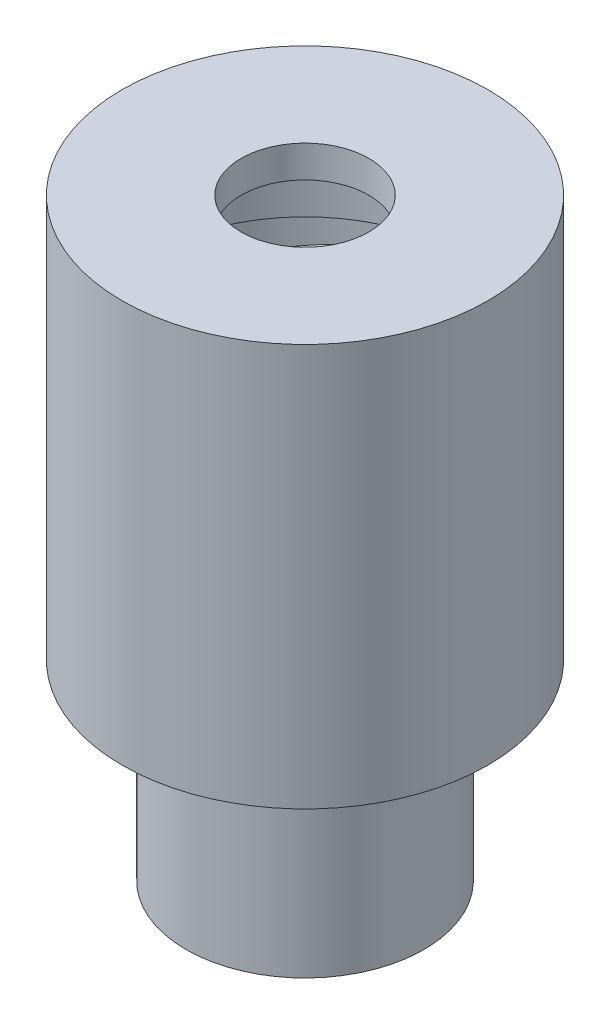
SolidWorks part; units mm, degrees
ref_plane "Front Plane" through (0, 0, 0) normal (0, 0, 1) x (1, 0, 0)
ref_plane "Top Plane" through (0, 0, 0) normal (0, 1, 0) x (1, 0, 0)
ref_plane "Right Plane" through (0, 0, 0) normal (1, 0, 0) x (0, 0, -1)
sketch "Sketch1" plane through (0, 0, 0) normal (0, 1, 0) x (1, 0, 0)
  circle A0 centre (0, 0) radius 18.64
extrude "Boss-Extrude2" add sketch "Sketch1" along normal blind 30
sketch "Sketch2" plane through (0, 30, 0) normal (0, 1, 0) x (1, 0, 0)
  circle A0 centre (0, 0) radius 28.64
  circle A1 centre (0, 0) radius 18.64 construction
  dimension "D1" = 10
extrude "Boss-Extrude3" add sketch "Sketch2" along normal blind 15
sketch "Sketch3" plane through (0, 45, 0) normal (0, 1, 0) x (1, 0, 0)
  circle A0 centre (0, 0) radius 26.64
  circle A1 centre (0, 0) radius 28.64
  dimension "D1" = 2
  dimension "D2" = 57.28
extrude "Boss-Extrude4" add sketch "Sketch3" along normal blind 45
chamfer "Chamfer1" distance 2 angle 45 1 edges at (0, 90, 26.64)
sketch "Sketch4" plane through (0, 0, 0) normal (0, 1, 0) x (1, 0, 0)
  circle A0 centre (0, 0) radius 28.64
extrude "Boss-Extrude5" add sketch "Sketch4" along normal blind 5 from offset 88 separate body
chamfer "Chamfer2" distance 2 angle 45 1 edges at (0, 88, 28.64)
sketch "Sketch5" plane through (0, 88, 0) normal (0, -1, 0) x (1, 0, 0)
  circle A0 centre (0, 0) radius 24.14
  circle A1 centre (0, 0) radius 26.64
  dimension "D1" = 53.28
  dimension "D2" = 2.5
extrude "Boss-Extrude6" add sketch "Sketch5" along normal blind 15
sketch "Sketch10" plane through (0, 73, 0) normal (0, -1, 0) x (1, 0, 0)
  circle A0 centre (0, 0) radius 25.39
  circle A1 centre (0, 0) radius 26.64 construction
  dimension "D1" = 1.25
curve "Helix/Spiral2" pitch 15 height 14.25 radius 25.39 left hand yes centre (0, 73, 0) axis (0, -1, 0) start towards (1, 0, 0)
ref_plane "Plane3" through (0, 0, 0) normal (0, 0, 1) x (1, 0, 0)
sketch "Sketch14" plane through (0, 0, 0) normal (0, 0, 1) x (1, 0, 0)
  line L0 (-26.64, 73) -> (26.64, 73) construction
  line L1 (26.6095, 73) -> (24.1095, 73)
  line L2 (26.6095, 73) -> (26.6095, 68)
  line L3 (26.6095, 68) -> (24.1095, 68)
  line L4 (24.1095, 73) -> (24.1095, 68)
  line L5 (26.6095, 73) -> (24.1095, 68) construction
  line L6 (26.6095, 68) -> (24.1095, 73) construction
  point P4 (25.3595, 70.5)
  dimension "D1" = 2.5
  dimension "D2" = 5
sweep "Sweep2" add profiles "Sketch14" path "Helix/Spiral2"
sketch "Sketch15" plane through (0, 93, 0) normal (0, 1, 0) x (1, 0, 0)
  circle A0 centre (0, 0) radius 10
  dimension "D1" = 20
extrude "Cut-Extrude1" cut sketch "Sketch15" against normal blind 15
